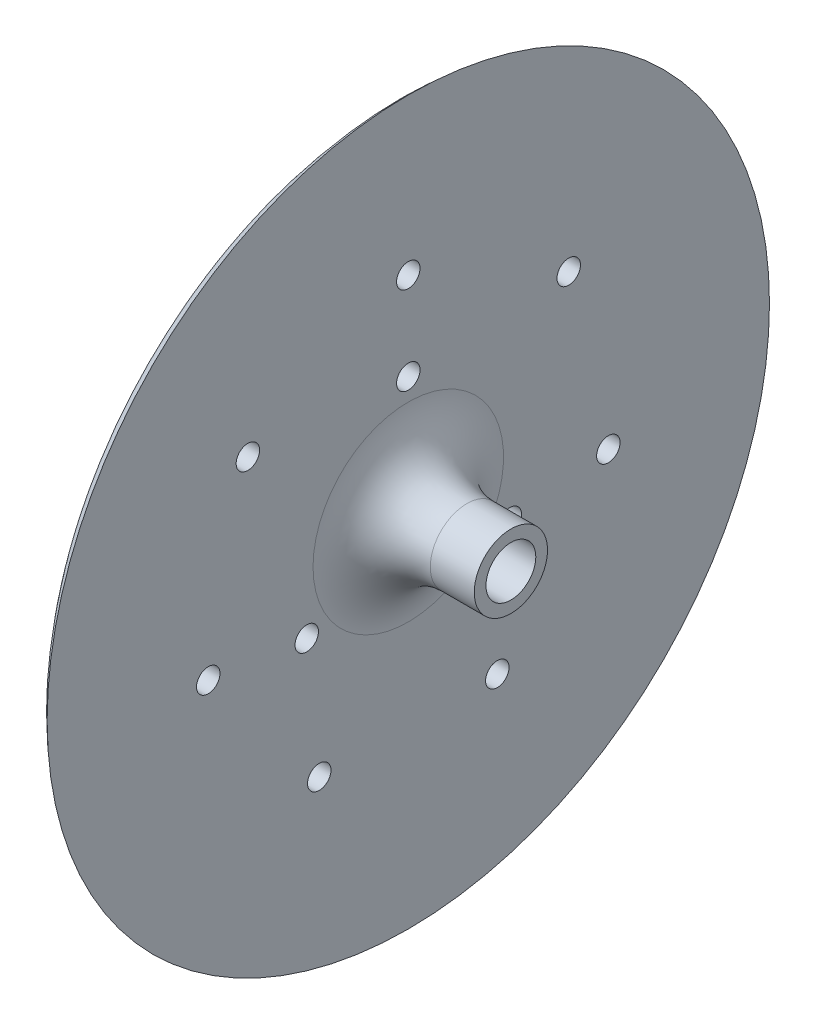
SolidWorks part; units mm, degrees
ref_plane "前视基准面" through (0, 0, 0) normal (0, 0, 1) x (1, 0, 0)
ref_plane "上视基准面" through (0, 0, 0) normal (0, 1, 0) x (1, 0, 0)
ref_plane "右视基准面" through (0, 0, 0) normal (1, 0, 0) x (0, 0, -1)
sketch "草图1" plane through (0, 0, 0) normal (0, 0, 1) x (1, 0, 0)
  line L0 (0, 0) -> (50, 0)
  line L1 (50, 0) -> (50, 12.5)
  line L2 (50, 12.5) -> (35, 12.5)
  line L3 (0, 0) -> (0, 50)
  line L4 (0, 50) -> (4, 50)
  line L5 (4, 50) -> (4, 100)
  line L6 (15, 123.2164) -> (15, 32.5)
  arc A0 (4, 100) -> (15, 123.2164) centre (34, 100) cw
  arc A1 (35, 12.5) -> (15, 32.5) centre (35, 32.5) cw
  dimension "D4" = 30
  dimension "D7" = 20
  dimension "D1" = 4
  dimension "D2" = 50
  dimension "D3" = 100
  dimension "D5" = 15
  dimension "D6" = 12.5
  dimension "D8" = 50
revolve "旋转1" add sketch "草图1" angle 360 about L0
sketch "草图3" plane through (50, 0, 0) normal (1, 0, 0) x (0, 0, -1)
  line L0 (-3, 7.953) -> (-3, 6)
  line L1 (-3, 6) -> (3, 6)
  line L2 (3, 6) -> (3, 7.953)
  line L3 (0, 0) -> (0, 14.3133) construction
  circle A0 centre (0, 0) radius 8.5
  point P7 (3, 6.9765)
  dimension "D1" = 17
  dimension "D2" = 6
  dimension "D3" = 6
extrude "切除-拉伸1" cut sketch "草图3" against normal blind 35 contours L0 A0 L2 L1 region at (50, -0.4682, 0)
extrude "切除-拉伸3" cut sketch "草图3<4>" against normal blind 5 contours L1 L3 A0 L0 | L3 L1 L2 A0 region at (50, 7.1657, 1.4415) region at (50, 7.1657, -1.4415)
sketch "草图3<4>" plane through (50, 0, 0) normal (1, 0, 0) x (0, 0, -1) same geometry as "草图3"
sketch "草图5" plane through (0, 0, 0) normal (-1, 0, 0) x (0, 0, 1)
  circle A0 centre (0, 0) radius 5
  dimension "D1" = 10
extrude "切除-拉伸4" cut sketch "草图5" against normal blind 25
sketch "草图6" plane through (15, 0, 0) normal (1, 0, 0) x (0, 0, -1)
  circle A1 centre (0, 0) radius 70 construction
  circle A2 centre (0, 70) radius 4
  point P26 (0, 0)
  point P35 (0, 0)
  dimension "D1" = 140
  dimension "D3" = 8
extrude "切除-拉伸5" cut sketch "草图6" against normal through all both and the other way through all
pattern_circular "阵列(圆周)1" count 7 over 360 about axis through (35, 0, 0) along (-1, 0, 0) of "切除-拉伸5"
sketch "草图7" plane through (15, 0, 0) normal (1, 0, 0) x (0, 0, -1)
  circle A0 centre (0, 0) radius 40 construction
  circle A1 centre (0, 40) radius 4
  dimension "D1" = 80
  dimension "D2" = 8
extrude "切除-拉伸6" cut sketch "草图7" against normal through all both and the other way through all
pattern_circular "阵列(圆周)2" count 3 over 360 about axis through (50, 0, 0) along (1, 0, 0) of "切除-拉伸6"
